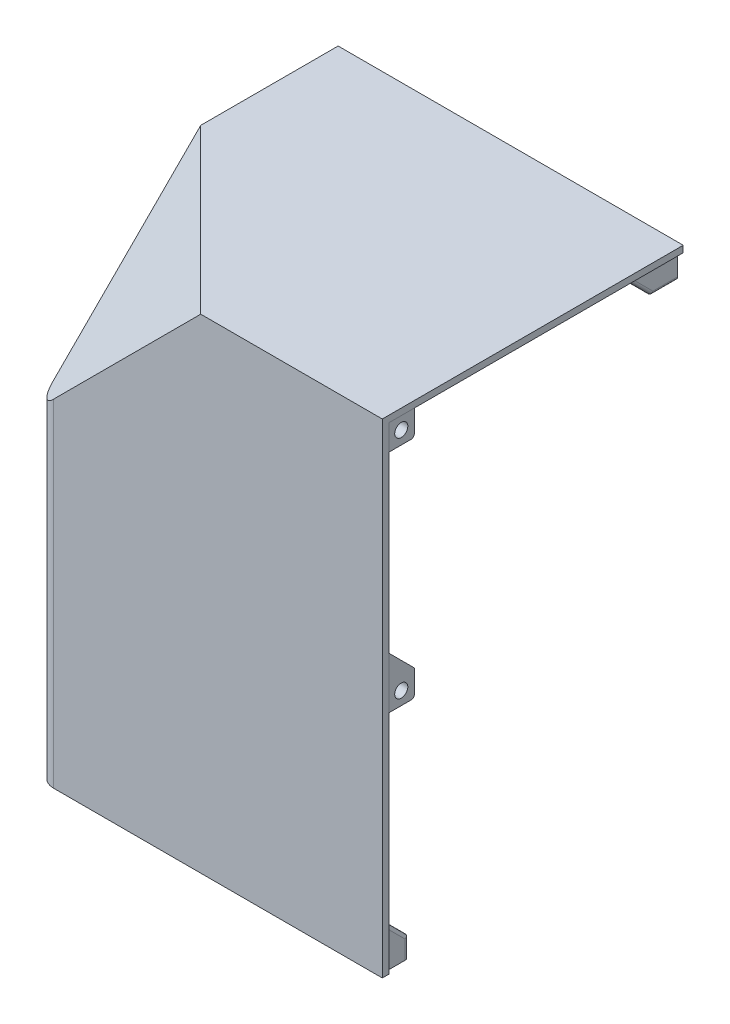
SolidWorks part; units mm, degrees
ref_plane "Front Plane" through (0, 0, 0) normal (0, 0, 1) x (1, 0, 0)
ref_plane "Top Plane" through (0, 0, 0) normal (0, 1, 0) x (1, 0, 0)
ref_plane "Right Plane" through (0, 0, 0) normal (1, 0, 0) x (0, 0, -1)
sketch "Sketch1" plane through (0, 0, 0) normal (0, 1, 0) x (1, 0, 0)
  line L0 (0, 0) -> (105.5, 0)
  line L1 (105.5, 0) -> (105.5, 2)
  line L2 (105.5, 2) -> (2, 2)
  line L3 (2, 2) -> (2, 92)
  line L4 (2, 92) -> (0, 92)
  line L5 (0, 92) -> (0, 0)
  dimension "D1" = 105.5
  dimension "D2" = 92
  dimension "D3" = 2
extrude "Boss-Extrude1" add sketch "Sketch1" along normal blind 146
sketch "Sketch2" plane through (0, 146, 0) normal (0, 1, 0) x (1, 0, 0)
  line L1 (0, 92) -> (105.5, 92)
  line L2 (0, 92) -> (0, 0)
  line L3 (0, 0) -> (105.5, 0)
  line L4 (105.5, 92) -> (105.5, 0)
extrude "Boss-Extrude2" add sketch "Sketch2" along normal blind 2
sketch "Sketch3" plane through (0, 0, 0) normal (0, -1, 0) x (1, 0, 0)
  line L0 (2, -76) -> (9, -76)
  line L1 (2, -2) -> (2, -92) construction
  line L2 (9, -76) -> (9, -84)
  line L3 (9, -84) -> (2, -84)
  line L4 (2, -84) -> (2, -76)
  line L5 (5, -80) -> (9, -80) construction
  line L8 (1, -1) -> (9, -1)
  line L9 (1, -1) -> (1, -9)
  line L10 (1, -9) -> (9, -9)
  line L11 (9, -1) -> (9, -9)
  line L12 (1, -1) -> (9, -9) construction
  line L13 (1, -9) -> (9, -1) construction
  line L14 (96.5, -1) -> (104.5, -1)
  line L15 (96.5, -1) -> (96.5, -9)
  line L16 (96.5, -9) -> (104.5, -9)
  line L17 (104.5, -1) -> (104.5, -9)
  line L18 (96.5, -1) -> (104.5, -9) construction
  line L19 (96.5, -9) -> (104.5, -1) construction
  circle A0 centre (5, -80) radius 3.47 construction
  circle A1 centre (5, -80) radius 3.47 construction
  circle A2 centre (5, -80) radius 2
  circle A3 centre (5, -5) radius 3.47 construction
  circle A4 centre (5, -5) radius 3.47 construction
  circle A5 centre (100.5, -5) radius 3.47 construction
  circle A6 centre (100.5, -5) radius 3.47 construction
  circle A7 centre (5, -5) radius 2
  circle A8 centre (100.5, -5) radius 2
  dimension "D3" = 4
  dimension "D4" = 8
  dimension "D1" = 7
  dimension "D2" = 8
extrude "Boss-Extrude3" add sketch "Sketch3" against normal blind 6 from offset 0.2 offset against normal yes
sketch "Sketch4" plane through (0, 0, -2) normal (0, 0, -1) x (-1, 0, 0)
  line L0 (-110, 145.47) -> (-110, 138.53) construction
  line L1 (-110, 76.47) -> (-110, 69.53) construction
  line L2 (-110, 145.47) -> (-110, 138.53) construction
  line L3 (-110, 76.47) -> (-110, 69.53) construction
  line L4 (-110, 73) -> (-97.5, 73) construction
  line L5 (-110, 142) -> (-69.0955, 142) construction
  line L6 (-105.5, 146) -> (-105.5, 0) construction
  line L7 (-105.5, 146) -> (-105.5, 0) construction
  line L8 (-105.5, 146) -> (-2, 146) construction
  line L9 (-105.5, 69) -> (-97.5, 69)
  line L10 (-105.5, 69) -> (-105.5, 77)
  line L11 (-105.5, 77) -> (-97.5, 77)
  line L12 (-97.5, 69) -> (-97.5, 77)
  line L13 (-105.5, 138) -> (-97.5, 138)
  line L14 (-105.5, 138) -> (-105.5, 146)
  line L15 (-105.5, 146) -> (-97.5, 146)
  line L16 (-97.5, 138) -> (-97.5, 146)
  point P22 (-97.5, 73)
  dimension "D1" = 8
  dimension "D2" = 8
extrude "Boss-Extrude4" add sketch "Sketch4" along normal blind 8
sketch "Sketch5" plane through (105.5, 0, 0) normal (1, 0, 0) x (0, 0, -1)
  line L0 (2, 146) -> (2, 6.2) construction
  line L1 (10, 69) -> (2, 69)
  line L2 (10, 69) -> (10, 146)
  line L3 (10, 146) -> (2, 146)
  line L4 (2, 69) -> (2, 146)
  line L5 (2, 146) -> (92, 146) construction
extrude "Cut-Extrude1" cut sketch "Sketch5" against normal blind 0.2
hole_wizard "Ø4.0mm Dowel Hole1" positions "Sketch6" profile "Sketch8" hole size "Ø4.0" standard "DIN" end condition up to next
sketch "Sketch6" plane through (105.3, 0, 0) normal (1, 0, 0) x (0, 0, -1)
  circle A0 centre (6, 142) radius 3.47 construction
  circle A1 centre (6, 73) radius 3.47 construction
  point P0 (6, 142)
  point P5 (6, 73)
sketch "Sketch8" plane through (105.3, 142, -6) normal (0, 1, 0) x (0, 0, -1)
  line L0 (0, 0) -> (0, 7.8)
  line L1 (0, 7.8) -> (2, 7.8)
  line L2 (2, 7.8) -> (2, 0)
  line L5 (2, 0) -> (0, 0)
  line L11 (0, -6.35) -> (0, 107.95) construction
  dimension "Thru Hole Dia." = 4
  dimension "Thru Hole Depth" = 7.8
chamfer "Chamfer2" distance 8 angle 45 2 edges at (97.5, 142, -2) (97.5, 73, -2)
sketch "Sketch9" plane through (0, 0, -92) normal (0, 0, -1) x (-1, 0, 0)
  line L0 (-105.5, 146) -> (-2, 146) construction
  line L1 (-2, 146) -> (-10, 146)
  line L2 (-2, 146) -> (-2, 138)
  line L3 (-2, 138) -> (-10, 138)
  line L4 (-10, 146) -> (-10, 138)
  line L5 (-104, 146) -> (-96, 146)
  line L6 (-104, 146) -> (-104, 138)
  line L7 (-104, 138) -> (-96, 138)
  line L8 (-96, 146) -> (-96, 138)
  line L10 (-100, 142) -> (-100, 138) construction
  line L13 (-10, 78) -> (-2, 78)
  line L14 (-10, 78) -> (-10, 86)
  line L15 (-10, 86) -> (-2, 86)
  line L16 (-2, 78) -> (-2, 86)
  line L17 (-10, 78) -> (-2, 86) construction
  line L18 (-10, 86) -> (-2, 78) construction
  circle A0 centre (-100, 142) radius 3.47 construction
  circle A1 centre (-6, 142) radius 3.47 construction
  circle A2 centre (-100, 142) radius 3.47 construction
  circle A3 centre (-6, 142) radius 3.47 construction
  circle A4 centre (-100, 142) radius 2
  circle A5 centre (-6, 142) radius 2
  circle A6 centre (-6, 82) radius 3.47 construction
  circle A7 centre (-6, 82) radius 3.47 construction
  circle A8 centre (-6, 82) radius 2
  dimension "D3" = 4
  dimension "D1" = 8
  dimension "D2" = 8
  dimension "D4" = 8
extrude "Boss-Extrude5" add sketch "Sketch9" against normal blind 8 from offset 0.2 offset against normal yes
chamfer "Chamfer3" distance 8 angle 45 3 edges at (6, 146, -83.8) (100, 146, -83.8) (97.4, 77, -2)
chamfer "Chamfer1" distance 7 angle 45 4 edges at (2, 6.2, -80) (100.5, 6.2, -2) (2, 6.2, -5.5) (2, 86, -87.8)
chamfer "Chamfer4" distance 7 angle 45 4 edges at (2, 6.7, -76) (96.5, 6.7, -2) (96, 146, -83.8) (2, 85.5, -83.8)
fillet "Fillet1" radius 1 16 edges at (9, 3.2, -84) (5.5, 9.7, -84) (9, 3.2, -9) (104.5, 3.2, -9) (104.5, 9.7, -5.5) (5.5, 9.7, -9) (93.5, 138, -6) (101.4, 138, -10) (101.4, 69, -10) (93.5, 69, -6) (96, 138.5, -83.3) (96, 138, -87.8) (104, 142, -79.8) (104, 138, -87.8) (10, 142, -79.8) (10, 138, -87.8)
sketch "Sketch13" plane through (0, 148, 0) normal (0, 1, 0) x (1, 0, 0)
  line L0 (0, 50) -> (0, 0)
  line L1 (0, 92) -> (0, 0) construction
  line L2 (0, 0) -> (50, 0)
  line L3 (0, 0) -> (105.5, 0) construction
  dimension "D1" = 50
sketch "Sketch14" plane through (0, 0, 0) normal (-1, 0, 0) x (0, 0, 1)
  line L0 (0, 148) -> (0, 98)
  line L1 (0, 148) -> (0, 0) construction
  line L2 (-50, 148) -> (0, 148) construction
ref_plane "Plane3" through (-32.6667, 32.6667, 32.6667) normal (-0.5774, 0.5774, 0.5774) x (0.8165, 0.4082, 0.4082)
sketch "Sketch15" plane through (-32.6667, 32.6667, 32.6667) normal (-0.5774, 0.5774, 0.5774) x (0.8165, 0.4082, 0.4082)
  circle A0 centre (60.4207, 104.6518) radius 50
  dimension "D1" = 100
extrude "Cut-Extrude4" cut sketch "Sketch15" along normal through all
sketch "Sketch16" plane through (-32.6667, 32.6667, 32.6667) normal (-0.5774, 0.5774, 0.5774) x (0.4082, -0.4082, 0.8165)
  line L3 (-101.2456, 104.6518) -> (-40.0083, 69.2965)
  line L4 (-40.0083, 69.2965) -> (-40.0083, 140.0071)
  line L5 (-40.0083, 140.0071) -> (-101.2456, 104.6518)
  line L6 (-101.2456, 104.6518) -> (-40.0083, 69.2965)
  line L7 (-40.0083, 69.2965) -> (-40.0083, 140.0071)
  line L8 (-40.0083, 140.0071) -> (-101.2456, 104.6518)
  dimension "D1" = 0
extrude "Boss-Extrude7" add sketch "Sketch16" against normal blind 3
fillet "Fillet2" radius 5 1 edges at (0, 49, 0)
